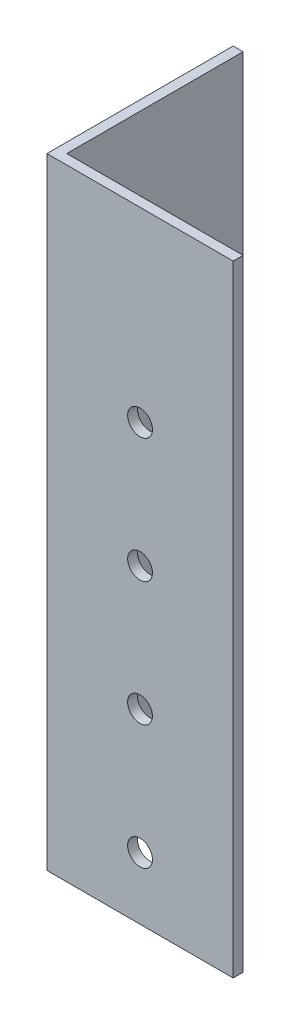
SolidWorks part; units mm, degrees
ref_plane "Спереди" through (0, 0, 0) normal (0, 0, 1) x (1, 0, 0)
ref_plane "Сверху" through (0, 0, 0) normal (0, 1, 0) x (1, 0, 0)
ref_plane "Справа" through (0, 0, 0) normal (1, 0, 0) x (0, 0, -1)
sketch "Эскиз1" plane through (0, 0, 0) normal (0, 1, 0) x (1, 0, 0)
  line L0 (0, 0) -> (75, 0)
  line L1 (0, 0) -> (0, 75)
extrude "Вытянуть-Тонкостенный1" add sketch "Эскиз1" along normal blind 250 thin thin type one direction wall 4
sketch "Эскиз6" plane through (0, 0, 0) normal (-1, 0, 0) x (0, 0, 1)
  circle A0 centre (-37.5, 25) radius 5
  circle A1 centre (-37.5, 75) radius 5
  circle A2 centre (-37.5, 125) radius 5
  circle A3 centre (-37.5, 175) radius 5
  dimension "D1" = 4
extrude "Вырез-Вытянуть1" cut sketch "Эскиз6" against normal blind 10
sketch "Эскиз7" plane through (0, 0, 0) normal (0, 0, 1) x (1, 0, 0)
  circle A0 centre (37.5, 25) radius 5
  circle A1 centre (37.5, 75) radius 5
  circle A2 centre (37.5, 125) radius 5
  circle A3 centre (37.5, 175) radius 5
  dimension "D1" = 4
extrude "Вырез-Вытянуть2" cut sketch "Эскиз7" against normal blind 10
